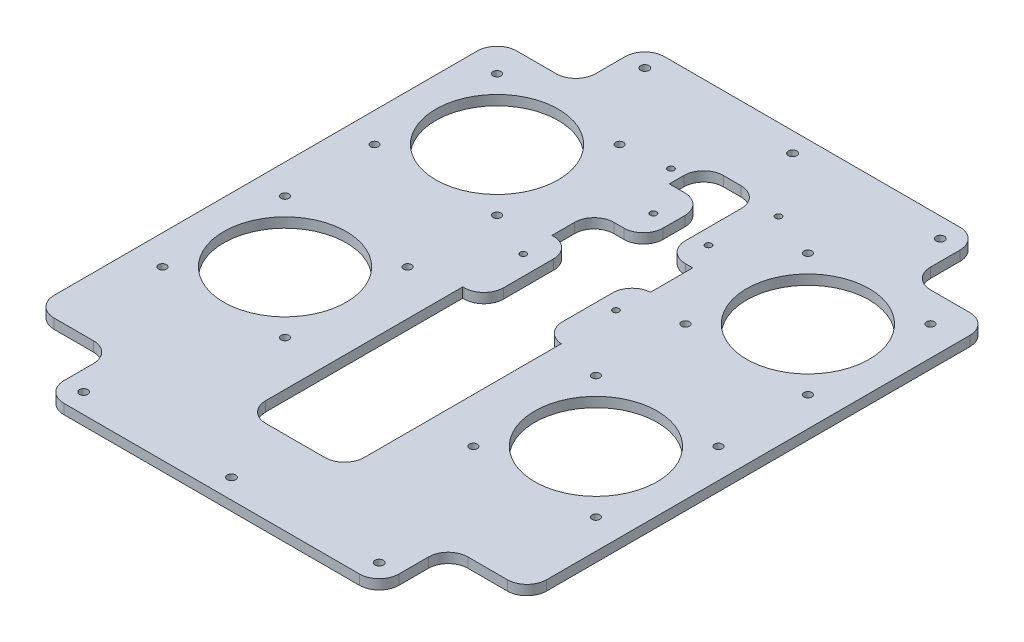
SolidWorks part; units mm, degrees
ref_plane "Front Plane" through (0, 0, 0) normal (0, 0, 1) x (1, 0, 0)
ref_plane "Top Plane" through (0, 0, 0) normal (0, 1, 0) x (1, 0, 0)
ref_plane "Right Plane" through (0, 0, 0) normal (1, 0, 0) x (0, 0, -1)
sketch "Sketch1" plane through (0, 0, 0) normal (0, 1, 0) x (1, 0, 0)
  line L1 (-139.7, 152.4) -> (139.7, 152.4)
  line L2 (-139.7, 152.4) -> (-139.7, -152.4)
  line L3 (-139.7, -152.4) -> (139.7, -152.4)
  line L4 (139.7, 152.4) -> (139.7, -152.4)
  line L5 (-139.7, 152.4) -> (139.7, -152.4) construction
  line L6 (-139.7, -152.4) -> (139.7, 152.4) construction
  point P0 (0, 0)
  dimension "D1" = 279.4
  dimension "D2" = 304.8
extrude "Boss-Extrude1" add sketch "Sketch1" along normal blind 5
sketch "Sketch2" plane through (0, 5, 0) normal (0, 1, 0) x (1, 0, 0)
  line L0 (-139.7, 152.4) -> (-85, 152.4)
  line L1 (139.7, 152.4) -> (-139.7, 152.4) construction
  line L2 (-85, 152.4) -> (-85, 117.4)
  line L3 (-85, 117.4) -> (-125, 117.4)
  line L4 (-125, 117.4) -> (-125, -117.4)
  line L5 (-125, -117.4) -> (-85, -117.4)
  line L6 (-85, -117.4) -> (-85, -152.4)
  line L7 (-139.7, -152.4) -> (139.7, -152.4) construction
  line L8 (0, -152.4) -> (0, 152.4) construction
  line L9 (-139.7, 152.4) -> (-139.7, -152.4)
  line L10 (-139.7, -152.4) -> (-85, -152.4)
  line L11 (139.7, -152.4) -> (85, -152.4)
  line L12 (139.7, 152.4) -> (139.7, -152.4)
  line L13 (85, -117.4) -> (85, -152.4)
  line L14 (125, -117.4) -> (85, -117.4)
  line L15 (125, 117.4) -> (125, -117.4)
  line L16 (85, 117.4) -> (125, 117.4)
  line L17 (85, 152.4) -> (85, 117.4)
  line L18 (139.7, 152.4) -> (85, 152.4)
  dimension "D1" = 35
  dimension "D2" = 85
  dimension "D3" = 125
extrude "Cut-Extrude1" cut sketch "Sketch2" against normal blind 10
sketch "Sketch3" plane through (0, 5, 0) normal (0, 1, 0) x (1, 0, 0)
  line L1 (75, -142.4) -> (-75, -142.4) construction
  line L2 (75, -142.4) -> (75, 142.4) construction
  line L3 (75, 142.4) -> (-75, 142.4) construction
  line L4 (-75, -142.4) -> (-75, 142.4) construction
  line L5 (75, -142.4) -> (-75, 142.4) construction
  line L6 (75, 142.4) -> (-75, -142.4) construction
  line L7 (-85, 152.4) -> (-75, 152.4) construction
  line L8 (-85, 152.4) -> (-85, 142.4) construction
  line L9 (-85, 142.4) -> (-75, 142.4) construction
  line L10 (-75, 152.4) -> (-75, 142.4) construction
  circle A0 centre (-75, 142.4) radius 2.125
  circle A1 centre (75, 142.4) radius 2.125
  circle A2 centre (75, -142.4) radius 2.125
  circle A3 centre (-75, -142.4) radius 2.125
  circle A4 centre (0, 142.4) radius 2.125
  circle A5 centre (0, -142.4) radius 2.125
  point P0 (0, 0)
  dimension "D1" = 4.25
  dimension "D2" = 10
extrude "Cut-Extrude2" cut sketch "Sketch3" against normal through all
sketch "Sketch5" plane through (0, 5, 0) normal (0, 1, 0) x (1, 0, 0)
  line L0 (0, 66.7278) -> (-25, 66.7278)
  line L1 (25, -110) -> (-25, -110)
  line L2 (25, -110) -> (25, 0)
  line L4 (25, 0) -> (15.6445, 0)
  line L5 (-25, -110) -> (-25, 0)
  line L6 (25, -110) -> (-25, 0) construction
  line L7 (25, 0) -> (-25, -110) construction
  line L8 (25, 66.7278) -> (11.2133, 66.7278)
  line L9 (25, 66.7278) -> (25, 45.3101)
  line L10 (25, 45.3101) -> (15.6445, 45.3101)
  line L11 (-25, 66.7278) -> (-25, 45.3101)
  line L12 (25, 66.7278) -> (-25, 45.3101) construction
  line L13 (25, 45.3101) -> (-25, 66.7278) construction
  line L15 (-14.2665, 0) -> (-14.2665, 45.3101)
  line L16 (-14.2665, 0) -> (-25, 0)
  line L17 (15.6445, 0) -> (15.6445, 45.3101)
  line L18 (-14.2665, 45.3101) -> (-25, 45.3101)
  line L19 (11.2133, 66.7278) -> (11.2133, 115.1025)
  line L20 (11.2133, 115.1025) -> (0, 115.1025)
  line L21 (0, 66.7278) -> (0, 97.6885)
  line L22 (0, 115.1025) -> (-17.8494, 115.1025)
  line L24 (0, 97.6885) -> (-17.8494, 97.6885)
  line L25 (-17.8494, 115.1025) -> (-17.8494, 97.6885)
  circle A0 centre (24.1206, 111.1375) radius 1.5875
  circle A1 centre (-24.1394, 104.7875) radius 1.5875
  circle A2 centre (-8.8994, 80.6575) radius 1.5875
  circle A3 centre (19.0406, 80.6575) radius 1.5875
  circle A4 centre (24.1206, 28.5875) radius 1.5875
  circle A5 centre (-24.1394, 29.8575) radius 1.5875
  point P19 (0, -55)
  point P24 (0, 0)
  point P25 (0, 56.0189)
sketch "Sketch6" plane through (0, 5, 0) normal (0, 1, 0) x (1, 0, 0)
  line L0 (-125, -117.4) -> (-125, 117.4) construction
  line L1 (-47.8, 102.4) -> (-110, 102.4) construction
  line L2 (-47.8, 102.4) -> (-47.8, 40.2) construction
  line L3 (-47.8, 40.2) -> (-110, 40.2) construction
  line L4 (-110, 102.4) -> (-110, 40.2) construction
  line L5 (-47.8, 102.4) -> (-110, 40.2) construction
  line L6 (-47.8, 40.2) -> (-110, 102.4) construction
  line L7 (-125, 117.4) -> (-85, 117.4) construction
  line L8 (0, 152.4) -> (0, -152.4) construction
  line L9 (85, 152.4) -> (-85, 152.4) construction
  line L10 (-85, -152.4) -> (85, -152.4) construction
  line L11 (-47.8, -5.2) -> (-110, -5.2) construction
  line L13 (-47.8, -5.2) -> (-47.8, -67.4) construction
  line L14 (-47.8, -67.4) -> (-110, -67.4) construction
  line L15 (-110, -5.2) -> (-110, -67.4) construction
  line L16 (-47.8, -5.2) -> (-110, -67.4) construction
  line L17 (-47.8, -67.4) -> (-110, -5.2) construction
  line L18 (-85, -117.4) -> (-125, -117.4) construction
  line L19 (47.8, -67.4) -> (110, -5.2) construction
  line L20 (47.8, -5.2) -> (110, -67.4) construction
  line L21 (110, -5.2) -> (110, -67.4) construction
  line L22 (47.8, -67.4) -> (110, -67.4) construction
  line L23 (47.8, -5.2) -> (47.8, -67.4) construction
  line L24 (47.8, -5.2) -> (110, -5.2) construction
  line L25 (47.8, 40.2) -> (110, 102.4) construction
  line L26 (47.8, 102.4) -> (110, 40.2) construction
  line L27 (110, 102.4) -> (110, 40.2) construction
  line L28 (47.8, 40.2) -> (110, 40.2) construction
  line L29 (47.8, 102.4) -> (47.8, 40.2) construction
  line L30 (47.8, 102.4) -> (110, 102.4) construction
  circle A0 centre (-110, 102.4) radius 2
  circle A1 centre (-47.8, 102.4) radius 2
  circle A2 centre (-47.8, 40.2) radius 2
  circle A3 centre (-110, 40.2) radius 2
  circle A4 centre (-110, -5.2) radius 2
  circle A5 centre (-47.8, -5.2) radius 2
  circle A6 centre (-47.8, -67.4) radius 2
  circle A7 centre (-110, -67.4) radius 2
  circle A8 centre (-78.9, 71.3) radius 31.1
  circle A9 centre (-78.9, -36.3) radius 31.1
  circle A10 centre (78.9, -36.3) radius 31.1
  circle A11 centre (78.9, 71.3) radius 31.1
  circle A12 centre (110, -67.4) radius 2
  circle A13 centre (47.8, -67.4) radius 2
  circle A14 centre (47.8, -5.2) radius 2
  circle A15 centre (110, -5.2) radius 2
  circle A16 centre (110, 40.2) radius 2
  circle A17 centre (47.8, 40.2) radius 2
  circle A18 centre (47.8, 102.4) radius 2
  circle A19 centre (110, 102.4) radius 2
  point P0 (-78.9, 71.3)
  point P19 (-78.9, -36.3)
  dimension "D1" = 4
  dimension "D2" = 15
  dimension "D3" = 15
  dimension "D4" = 62.2
  dimension "D5" = 62.2
  dimension "D6" = 50
extrude "Cut-Extrude3" cut sketch "Sketch6" against normal through all
extrude "Cut-Extrude4" cut sketch "Sketch5" against normal blind 10
fillet "Fillet1" radius 10 24 edges at (125, 2.5, 117.4) (125, 2.5, -117.4) (85, 2.5, -117.4) (85, 2.5, -152.4) (-85, 2.5, -152.4) (-125, 2.5, -117.4) (-125, 2.5, 117.4) (-85, 2.5, 117.4) (-85, 2.5, 152.4) (85, 2.5, 152.4) (85, 2.5, 117.4) (-85, 2.5, -117.4) (25, 2.5, 110) (-25, 2.5, 110) (-14.2665, 2.5, 0) (15.6445, 2.5, 0) (-25, 2.5, -66.7278) (-14.2665, 2.5, -45.3101) (15.6445, 2.5, -45.3101) (0, 2.5, -66.7278) (11.2133, 2.5, -66.7278) (11.2133, 2.5, -115.1025) (-17.8494, 2.5, -115.1025) (0, 2.5, -97.6885)
